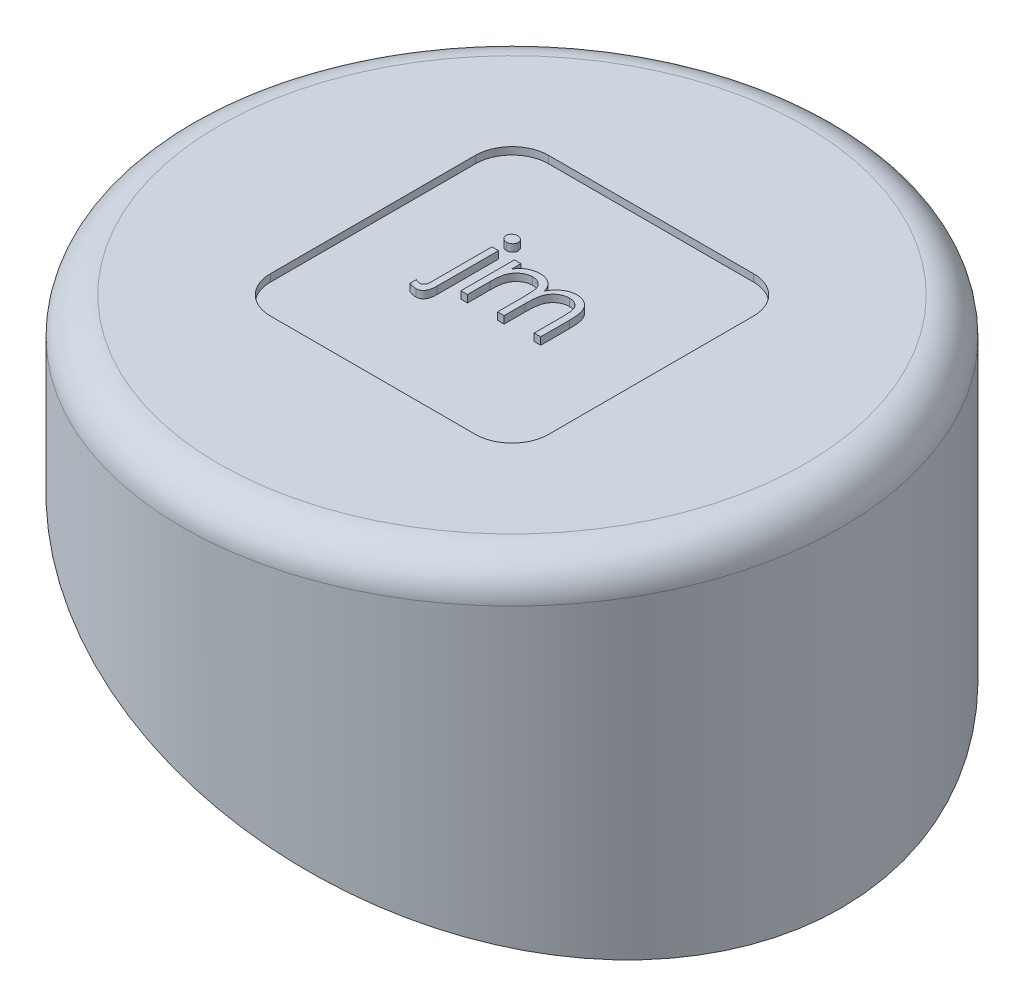
SolidWorks part; units mm, degrees
ref_plane "Front Plane" through (0, 0, 0) normal (0, 0, 1) x (1, 0, 0)
ref_plane "Top Plane" through (0, 0, 0) normal (0, 1, 0) x (1, 0, 0)
ref_plane "Right Plane" through (0, 0, 0) normal (1, 0, 0) x (0, 0, -1)
sketch "Sketch1" plane through (0, 0, 0) normal (0, 1, 0) x (1, 0, 0)
  circle A0 centre (0, 0) radius 45
  dimension "D1" = 90
extrude "Boss-Extrude1" add sketch "Sketch1" along normal blind 50
sketch "Sketch2" plane through (0, 0, 0) normal (0, 0, 1) x (1, 0, 0)
  line L0 (45, 0) -> (-45, 0)
  line L1 (-45, 0) -> (-45, 30.9895)
  line L2 (-45, 50) -> (-45, 0) construction
  line L3 (-45, 30.9895) -> (45, 0)
  dimension "D1" = 19
extrude "Cut-Extrude1" cut sketch "Sketch2" against normal up to body and the other way up to body separate body
fillet "Fillet1" radius 5 1 edges at (0, 50, 45)
shell "Shell1" thickness 2.5 removed face at (45, 0, 0)
sketch "Sketch3" plane through (0, 50, 0) normal (0, 1, 0) x (1, 0, 0)
  line L0 (-19, -3) -> (19, -3) construction
  line L1 (-14, -19) -> (14, -19)
  line L2 (-19, -14) -> (-19, 14)
  line L3 (-14, 19) -> (14, 19)
  line L4 (19, -14) -> (19, 14)
  line L5 (-19, -19) -> (19, 19) construction
  line L6 (-19, 19) -> (19, -19) construction
  line L7 (0, -19) -> (0, -3) construction
  arc A0 (-14, -19) -> (-19, -14) centre (-14, -14) cw
  arc A1 (14, -19) -> (19, -14) centre (14, -14) ccw
  arc A2 (14, 19) -> (19, 14) centre (14, 14) cw
  arc A3 (-19, 14) -> (-14, 19) centre (-14, 14) cw
  text T0 "jm" font "Century Gothic" height 10
  point P0 (0, 0)
  point P23 (0, -4.4882)
  dimension "D2" = 5
  dimension "D1" = 38
  dimension "D3" = 16
extrude "Cut-Extrude2" cut sketch "Sketch3" against normal blind 1
